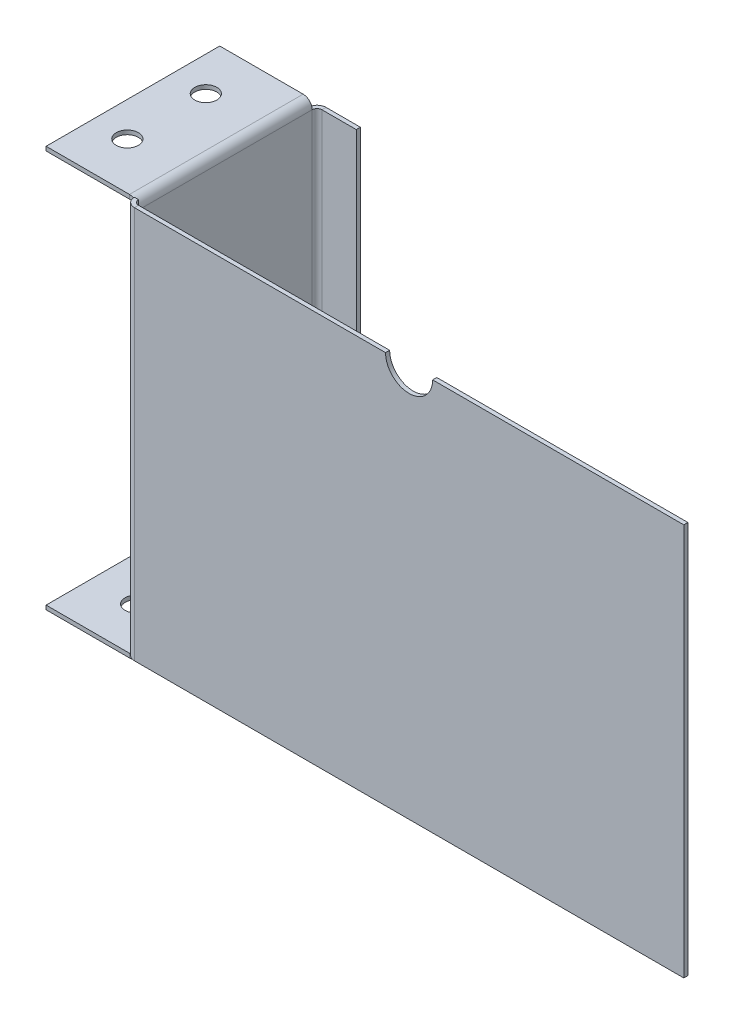
SolidWorks part; units mm, degrees
note: The reader was unsure of these and kept them because the rebuilt part matched: flange length of "Edge-Flange1", "Edge-Flange2", "Edge-Flange3", "Edge-Flange4".
material "Plain Carbon Steel"
ref_plane "Front Plane" through (0, 0, 0) normal (0, 0, 1) x (1, 0, 0)
ref_plane "Top Plane" through (0, 0, 0) normal (0, 1, 0) x (1, 0, 0)
ref_plane "Right Plane" through (0, 0, 0) normal (1, 0, 0) x (0, 0, -1)
sketch "Sketch1" plane through (0, 0, 0) normal (0, 0, 1) x (1, 0, 0)
  line L0 (0, 76.2) -> (355.6, 76.2) construction
  line L1 (0, 0) -> (355.6, 0)
  line L2 (0, 0) -> (0, 254)
  line L3 (0, 254) -> (162.56, 254)
  line L4 (355.6, 0) -> (355.6, 254)
  line L5 (177.8, 254) -> (177.8, 0) construction
  line L6 (193.04, 254) -> (355.6, 254)
  line L7 (162.56, 254) -> (177.8, 254) construction
  line L8 (177.8, 254) -> (193.04, 254) construction
  arc A0 (162.56, 254) -> (193.04, 254) centre (177.8, 254) ccw
  dimension "D4" = 15.24
  dimension "D1" = 355.6
  dimension "D2" = 254
  dimension "D3" = 177.8
base flange "Base-Flange1" sketch "Sketch1" thickness 2.6568 reverse thickness direction no parameters "D1"=3.175
edge flange "Edge-Flange1" sketch "Sketch8" flange angle 90 flange length 115.57 flange position bend outside bend radius 3.175 thickness 2.6568 relief rectangular parameters "D6"=10
sketch "Sketch8" plane through (0, 0, -2.6568) normal (-1, 0, 0) x (0, 1, 0)
  line L0 (254, 0) -> (0, 0) construction
  line L1 (254, 0) -> (0, 0)
  line L2 (0, 0) -> (0, 115.57)
  line L3 (0, 115.57) -> (254, 115.57)
  line L4 (254, 115.57) -> (254, 0)
bend "EdgeBend1" bend radius 3.175 bend angle 90 parameters "D5"=1
edge flange "Edge-Flange2" sketch "Sketch11" flange angle 90 flange length 57.15 flange position material inside bend radius 3.175 thickness 2.6568 relief none parameters "D6"=10
sketch "Sketch11" plane through (-5.8318, 254, 0) normal (0, 1, 0) x (0, 0, -1)
  line L0 (5.8318, 0) -> (118.2268, 0) construction
  line L1 (5.8318, 0) -> (118.2268, 0)
  line L2 (5.8318, 0) -> (5.8318, 57.15)
  line L3 (5.8318, 57.15) -> (118.2268, 57.15)
  line L4 (118.2268, 57.15) -> (118.2268, 0)
bend "EdgeBend2" bend radius 3.175 bend angle 90 parameters "D5"=2
edge flange "Edge-Flange3" sketch "Sketch14" flange angle 90 flange length 57.15 flange position bend outside bend radius 3.175 thickness 2.6568 relief rectangular parameters "D6"=10
sketch "Sketch14" plane through (-5.8318, 0, 0) normal (0, -1, 0) x (0, 0, 1)
  line L0 (-118.2268, 0) -> (-5.8318, 0) construction
  line L1 (-118.2268, 0) -> (-5.8318, 0)
  line L2 (-118.2268, 0) -> (-118.2268, 57.15)
  line L3 (-118.2268, 57.15) -> (-5.8318, 57.15)
  line L4 (-5.8318, 57.15) -> (-5.8318, 0)
bend "EdgeBend3" bend radius 3.175 bend angle 90 parameters "D5"=3
edge flange "Edge-Flange4" sketch "Sketch17" flange angle 90 flange length 25.4 flange position bend outside bend radius 3.175 thickness 2.6568 relief rectangular parameters "D6"=10
sketch "Sketch17" plane through (-3.175, 0, -118.2268) normal (0, 0, 1) x (0, -1, 0)
  line L2 (-248.1682, 0) -> (-248.1682, 25.4)
  line L3 (-248.1682, 25.4) -> (0, 25.4)
  line L4 (0, 25.4) -> (0, 0)
  line L5 (0, 0) -> (-248.1682, 0) construction
  line L6 (0, 0) -> (-248.1682, 0)
bend "EdgeBend4" bend radius 3.175 bend angle 90 parameters "D5"=4
sketch "Sketch22" plane through (0, 254, 0) normal (0, 1, 0) x (1, 0, 0)
  line L0 (-40.7645, 118.2268) -> (-40.7645, 5.8318) construction
  line L1 (-62.9818, 5.8318) -> (-9.0068, 5.8318) construction
  line L2 (-9.0068, 118.2268) -> (-62.9818, 118.2268) construction
  line L3 (-62.9818, 118.2268) -> (-62.9818, 5.8318) construction
  circle A0 centre (-40.7645, 86.995) radius 7.1437
  circle A1 centre (-40.7645, 36.195) radius 7.1437
  dimension "D2" = 14.2875
  dimension "D1" = 22.2174
  dimension "D3" = 50.8
  dimension "D4" = 31.2318
extrude "Cut-Extrude1" cut sketch "Sketch22" along direction (0, -1, 0) on the side against the normal up to next (2.6568 mm away) normal cut yes
sketch "Sketch23" plane through (0, -3.175, 0) normal (0, 1, 0) x (1, 0, 0)
  line L0 (-34.4068, 118.2268) -> (-34.4068, 5.8318) construction
  line L1 (-62.9818, 118.2268) -> (-9.0068, 118.2268) construction
  line L2 (-9.0068, 5.8318) -> (-62.9818, 5.8318) construction
  line L3 (-9.0068, 118.2268) -> (-9.0068, 5.8318) construction
  circle A0 centre (-34.4068, 86.36) radius 7.1438
  circle A1 centre (-34.4068, 35.56) radius 7.1438
  dimension "D4" = 14.2875
  dimension "D1" = 25.4
  dimension "D2" = 50.8
  dimension "D3" = 29.7282
extrude "Cut-Extrude2" cut sketch "Sketch23" along direction (0, 1, 0) on the side against the normal up to next (2.6568 mm away) normal cut yes
sketch "Sketch24" plane through (-5.8318, 0, 0) normal (-1, 0, 0) x (0, 0, 1)
  line L0 (-62.0293, 248.1682) -> (-62.0293, 76.2) construction
  line L1 (-118.2268, 248.1682) -> (-5.8318, 248.1682) construction
  line L2 (-62.0293, 76.2) -> (-62.0293, 41.7932) construction
  line L3 (-118.2268, 41.7932) -> (-5.8318, 41.7932) construction
  line L4 (-118.2268, 248.1682) -> (-118.2268, 0) construction
  line L5 (-5.8318, 248.1682) -> (-5.8318, 0) construction
  line L6 (-118.2268, 254) -> (-5.8318, 254) construction
  circle A0 centre (-86.995, 41.7932) radius 7.1438
  circle A1 centre (-34.4068, 41.7932) radius 7.1438
  dimension "D3" = 14.2875
  dimension "D1" = 177.8
  dimension "D2" = 34.4068
  dimension "D4" = 31.2318
  dimension "D5" = 52.5882
extrude "Cut-Extrude3" cut sketch "Sketch24" along direction (1, 0, 0) on the side against the normal up to next (2.6568 mm away) normal cut yes
sketch "Bend-Lines1" [suppressed] plane through (0, 0, 0) normal (0, 1, 0) x (1, 0, 0)
sketch "Bounding-Box1" [suppressed] plane through (0, 0, 0) normal (0, 1, 0) x (1, 0, 0)
sheet metal parameters "Sheet-Metal1" thickness 2.6568 parameters "D1"=3.175
flat pattern "Flat-Pattern1" [suppressed]
sketch "Bend-Lines2" plane through (0, 0, 0) normal (0, 1, 0) x (1, 0, 0)
sketch3d "Bounding-Box2" [suppressed]
  line L0 (0, 0, 0) -> (-355.6, 0, 0) construction
  line L1 (0, 254, 0) -> (-355.6, 254, 0) construction
  line L2 (0, 0, 0) -> (0, 254, 0) construction
  line L3 (-355.6, 0, 0) -> (-355.6, 254, 0) construction
sheet metal parameters "Sheet-Metal2" thickness 2.6568 parameters "D1"=3.175
flat pattern "Flat-Pattern1"
sketch "Bend-Lines2" plane through (0, 0, 0) normal (0, 0, 1) x (1, 0, 0)
  line L0 (-3.537, 254) -> (-3.537, 0) construction
  line L1 (-3.537, 254) -> (-3.537, 0) construction
sketch3d "Bounding-Box2" [suppressed]
  line L0 (-123.5965, 0, 0) -> (355.6, 0, 0) construction
  line L1 (-123.5965, 254, 0) -> (355.6, 254, 0) construction
  line L2 (-123.5965, 0, 0) -> (-123.5965, 254, 0) construction
  line L3 (355.6, 0, 0) -> (355.6, 254, 0) construction
bend of the flat pattern "Flatten-<EdgeBend1>1"
sheet metal parameters "Sheet-Metal3" thickness 2.6568 parameters "D1"=3.175
flat pattern "Flat-Pattern1"
sketch "Bend-Lines2" plane through (0, 0, 0) normal (0, 0, 1) x (1, 0, 0)
  line L0 (-3.537, 254) -> (-3.537, 0) construction
  line L1 (-3.537, 254) -> (-3.537, 0) construction
  line L2 (-7.074, 251.7051) -> (-123.5965, 251.7051) construction
  line L3 (-7.074, 251.7051) -> (-123.5965, 251.7051) construction
sketch3d "Bounding-Box2" [suppressed]
  line L0 (-123.5965, 0, 0) -> (355.6, 0, 0) construction
  line L1 (-123.5965, 309.2171, 0) -> (355.6, 309.2171, 0) construction
  line L2 (-123.5965, 0, 0) -> (-123.5965, 309.2171, 0) construction
  line L3 (355.6, 0, 0) -> (355.6, 309.2171, 0) construction
bend of the flat pattern "Flatten-<EdgeBend1>1"
bend of the flat pattern "Flatten-<EdgeBend2>1"
sheet metal parameters "Sheet-Metal4" thickness 2.6568 parameters "D1"=3.175
flat pattern "Flat-Pattern1"
sketch "Bend-Lines2" plane through (0, 0, 0) normal (0, 0, 1) x (1, 0, 0)
  line L0 (-3.537, 254) -> (-3.537, 0) construction
  line L1 (-3.537, 254) -> (-3.537, 0) construction
  line L2 (-7.074, 251.7051) -> (-123.5965, 251.7051) construction
  line L3 (-7.074, 251.7051) -> (-123.5965, 251.7051) construction
  line L4 (-123.5965, -3.537) -> (-7.074, -3.537) construction
  line L5 (-123.5965, -3.537) -> (-7.074, -3.537) construction
sketch3d "Bounding-Box2" [suppressed]
  line L0 (-123.5965, -61.049, 0) -> (355.6, -61.049, 0) construction
  line L1 (-123.5965, 309.2171, 0) -> (355.6, 309.2171, 0) construction
  line L2 (-123.5965, -61.049, 0) -> (-123.5965, 309.2171, 0) construction
  line L3 (355.6, -61.049, 0) -> (355.6, 309.2171, 0) construction
bend of the flat pattern "Flatten-<EdgeBend1>1"
bend of the flat pattern "Flatten-<EdgeBend2>1"
bend of the flat pattern "Flatten-<EdgeBend3>1"
sheet metal parameters "Sheet-Metal5" thickness 2.6568 parameters "D1"=3.175
flat pattern "Flat-Pattern1" [suppressed]
sketch "Bend-Lines2" plane through (0, 0, 0) normal (0, 0, 1) x (1, 0, 0)
  line L0 (-3.537, 254) -> (-3.537, 0) construction
  line L1 (-3.537, 254) -> (-3.537, 0) construction
  line L2 (-7.074, 251.7051) -> (-119.469, 251.7051) construction
  line L3 (-7.074, 251.7051) -> (-119.469, 251.7051) construction
  line L4 (-119.469, -3.537) -> (-7.074, -3.537) construction
  line L5 (-119.469, -3.537) -> (-7.074, -3.537) construction
  line L6 (-123.0059, 248.1682) -> (-123.0059, 0) construction
  line L7 (-123.0059, 248.1682) -> (-123.0059, 0) construction
sketch3d "Bounding-Box2" [suppressed]
  line L0 (-326.5679, -315.049, 0) -> (177.8, -315.049, 0) construction
  line L1 (-326.5679, 55.2171, 0) -> (177.8, 55.2171, 0) construction
  line L2 (-326.5679, -315.049, 0) -> (-326.5679, 55.2171, 0) construction
  line L3 (177.8, -315.049, 0) -> (177.8, 55.2171, 0) construction
bend of the flat pattern "Flatten-<EdgeBend1>1"
bend of the flat pattern "Flatten-<EdgeBend2>1"
bend of the flat pattern "Flatten-<EdgeBend3>1"
bend of the flat pattern "Flatten-<EdgeBend4>1"
sketch "Sketch18-1" [suppressed] plane through (-1.2421, 246.2353, 0) normal (0, 0, 1) x (0, -1, 0)
  spline S2 degree 3 poles (-47.1137, -34.925) (-47.1137, -47.625) (-34.4137, -47.625) (-34.4137, -34.925) (-34.4137, -22.225) (-47.1137, -22.225) (-47.1137, -34.925) (-47.1137, -47.625) (-34.4137, -47.625) knots -0.5 0 0 0 0.5 0.5 0.5 1 1 1 1.5 1.5 1.5 weights 1 0.333333 0.333333 1 0.333333 0.333333 1 0.333333 0.333333 only from (-47.1137, -34.925) to (-47.1137, -34.925)
  spline S3 degree 3 poles (-47.1137, -86.995) (-47.1137, -99.695) (-34.4137, -99.695) (-34.4137, -86.995) (-34.4137, -74.295) (-47.1137, -74.295) (-47.1137, -86.995) (-47.1137, -99.695) (-34.4137, -99.695) knots -0.5 0 0 0 0.5 0.5 0.5 1 1 1 1.5 1.5 1.5 weights 1 0.333333 0.333333 1 0.333333 0.333333 1 0.333333 0.333333 only from (-47.1137, -86.995) to (-47.1137, -86.995)
sheet metal parameters "Sheet-Metal8" thickness 2.6568 parameters "D1"=3.175
flat pattern "Flat-Pattern1"
sketch "Bend-Lines2" plane through (0, 0, 0) normal (0, 0, 1) x (1, 0, 0)
  line L0 (-3.537, 254) -> (-3.537, 0) construction
  line L1 (-3.537, 254) -> (-3.537, 0) construction
  line L2 (-7.074, 251.7051) -> (-119.469, 251.7051) construction
  line L3 (-7.074, 251.7051) -> (-119.469, 251.7051) construction
  line L4 (-119.469, -3.537) -> (-7.074, -3.537) construction
  line L5 (-119.469, -3.537) -> (-7.074, -3.537) construction
  line L6 (-123.0059, 248.1682) -> (-123.0059, 0) construction
  line L7 (-123.0059, 248.1682) -> (-123.0059, 0) construction
sketch3d "Bounding-Box2" [suppressed]
  line L0 (-326.5679, -315.049, 0) -> (177.8, -315.049, 0) construction
  line L1 (-326.5679, 55.2171, 0) -> (177.8, 55.2171, 0) construction
  line L2 (-326.5679, -315.049, 0) -> (-326.5679, 55.2171, 0) construction
  line L3 (177.8, -315.049, 0) -> (177.8, 55.2171, 0) construction
bend of the flat pattern "Flatten-<EdgeBend1>1"
bend of the flat pattern "Flatten-<EdgeBend2>1"
bend of the flat pattern "Flatten-<EdgeBend3>1"
bend of the flat pattern "Flatten-<EdgeBend4>1"
sheet metal parameters "Sheet-Metal9" thickness 2.6568 parameters "D1"=3.175
flat pattern "Flat-Pattern1"
sketch "Bend-Lines2" plane through (0, 0, 0) normal (0, 0, 1) x (1, 0, 0)
  line L0 (-3.537, 254) -> (-3.537, 0) construction
  line L1 (-3.537, 254) -> (-3.537, 0) construction
  line L2 (-7.074, 251.7051) -> (-119.469, 251.7051) construction
  line L3 (-7.074, 251.7051) -> (-119.469, 251.7051) construction
  line L4 (-119.469, -3.537) -> (-7.074, -3.537) construction
  line L5 (-119.469, -3.537) -> (-7.074, -3.537) construction
  line L6 (-123.0059, 248.1682) -> (-123.0059, 0) construction
  line L7 (-123.0059, 248.1682) -> (-123.0059, 0) construction
sketch3d "Bounding-Box2" [suppressed]
  line L0 (-326.5679, -315.049, 0) -> (177.8, -315.049, 0) construction
  line L1 (-326.5679, 55.2171, 0) -> (177.8, 55.2171, 0) construction
  line L2 (-326.5679, -315.049, 0) -> (-326.5679, 55.2171, 0) construction
  line L3 (177.8, -315.049, 0) -> (177.8, 55.2171, 0) construction
bend of the flat pattern "Flatten-<EdgeBend1>1"
bend of the flat pattern "Flatten-<EdgeBend2>1"
bend of the flat pattern "Flatten-<EdgeBend3>1"
bend of the flat pattern "Flatten-<EdgeBend4>1"
sheet metal parameters "Sheet-Metal10" thickness 2.6568 parameters "D1"=3.175
flat pattern "Flat-Pattern1"
sketch "Bend-Lines2" plane through (0, 0, 0) normal (0, 0, 1) x (1, 0, 0)
  line L0 (-3.537, 254) -> (-3.537, 0) construction
  line L1 (-3.537, 254) -> (-3.537, 0) construction
  line L2 (-7.074, 251.7051) -> (-119.469, 251.7051) construction
  line L3 (-7.074, 251.7051) -> (-119.469, 251.7051) construction
  line L4 (-119.469, -3.537) -> (-7.074, -3.537) construction
  line L5 (-119.469, -3.537) -> (-7.074, -3.537) construction
  line L6 (-123.0059, 248.1682) -> (-123.0059, 0) construction
  line L7 (-123.0059, 248.1682) -> (-123.0059, 0) construction
sketch3d "Bounding-Box2" [suppressed]
  line L0 (-326.5679, -315.049, 0) -> (177.8, -315.049, 0) construction
  line L1 (-326.5679, 55.2171, 0) -> (177.8, 55.2171, 0) construction
  line L2 (-326.5679, -315.049, 0) -> (-326.5679, 55.2171, 0) construction
  line L3 (177.8, -315.049, 0) -> (177.8, 55.2171, 0) construction
bend of the flat pattern "Flatten-<EdgeBend1>1"
bend of the flat pattern "Flatten-<EdgeBend2>1"
bend of the flat pattern "Flatten-<EdgeBend3>1"
bend of the flat pattern "Flatten-<EdgeBend4>1"
